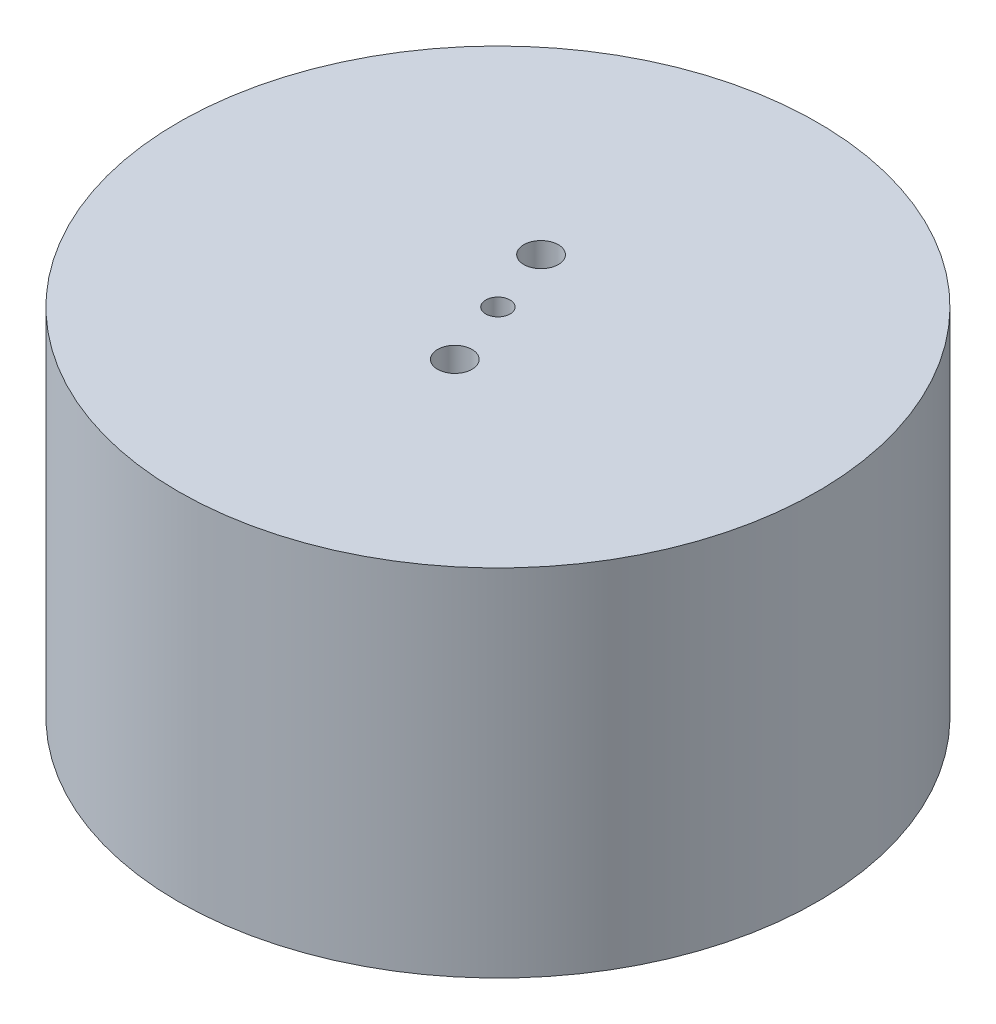
SolidWorks part; units mm, degrees
ref_plane "Front Plane" through (0, 0, 0) normal (0, 0, 1) x (1, 0, 0)
ref_plane "Top Plane" through (0, 0, 0) normal (0, 1, 0) x (1, 0, 0)
ref_plane "Right Plane" through (0, 0, 0) normal (1, 0, 0) x (0, 0, -1)
sketch "Sketch3" plane through (0, 0, 0) normal (0, 1, 0) x (1, 0, 0)
  circle A0 centre (0, 0) radius 26.5
  dimension "D1" = 53
sketch "Sketch4" plane through (0, 0, 0) normal (0, 1, 0) x (1, 0, 0)
  circle A0 centre (0, 0) radius 31.5
  circle A1 centre (0, 0) radius 26.5 construction
  dimension "D1" = 5
extrude "Boss-Extrude2" add sketch "Sketch4" along normal blind 35 contours A0
extrude "Cut-Extrude1" cut sketch "Sketch3" along normal blind 28 contours A0
sketch "Sketch5" plane through (0, 35, 0) normal (0, 1, 0) x (1, 0, 0)
  point P0 (0, 0)
sketch "Sketch7" plane through (0, 0, 0) normal (0, 0, 1) x (1, 0, 0)
  line L0 (0, 35) -> (0, 0)
hole_wizard "M3 Clearance Hole1" positions "Sketch9" profile "Sketch8" hole size "M3" standard "ANSI Metric"
sketch "Sketch9" plane through (0, 35, 0) normal (0, 1, 0) x (1, 0, 0)
  point P0 (-2.345, 6.5955)
  point P2 (2.345, -6.5955)
  dimension "D1" = 7
  dimension "D2" = 7
  dimension "D3" = 180
sketch "Sketch8" plane through (-2.345, 35, -6.5955) normal (1, 0, 0) x (0, 0, 1)
  line L0 (0, 0) -> (0, 51.0215)
  line L1 (0, 51.0215) -> (1.7, 50)
  line L2 (1.7, 50) -> (1.7, 0)
  line L5 (1.7, 0) -> (0, 0)
  line L10 (0, 51.0215) -> (-1.7, 50) construction
  line L11 (0, -6.35) -> (0, 107.95) construction
  dimension "Hole Dia." = 3.4
  dimension "Hole Depth" = 50
  dimension "Drill Angle" = 118
sketch "Sketch10" plane through (0, 35, 0) normal (0, 1, 0) x (1, 0, 0)
  circle A0 centre (0, 0) radius 1.2
extrude "Cut-Extrude2" cut sketch "Sketch10" against normal blind 10
